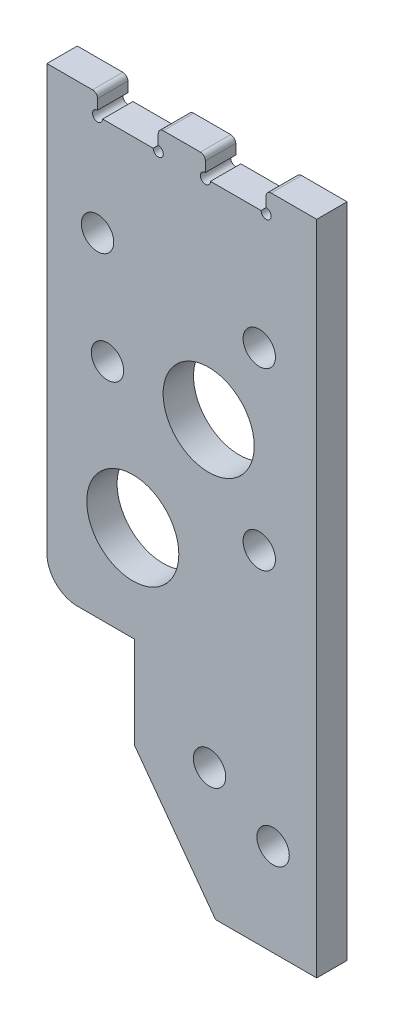
SolidWorks part; units mm, degrees
material "Thornel Mat VMA"
ref_plane "Front Plane" through (0, 0, 0) normal (0, 0, 1) x (1, 0, 0)
ref_plane "Top Plane" through (0, 0, 0) normal (0, 1, 0) x (1, 0, 0)
ref_plane "Right Plane" through (0, 0, 0) normal (1, 0, 0) x (0, 0, -1)
other "Configuration Table"
sketch "Sketch1" plane through (0, 0, 0) normal (0, 0, 1) x (1, 0, 0)
  line B0 (3.6623, 13.095) -> (3.6623, 3.9964)
  line B1 (3.6623, 3.9964) -> (11.6623, -6.905)
  line B2 (11.6623, -6.905) -> (21.6623, -6.905)
  line B3 (21.6623, -6.905) -> (21.6623, 13.095)
  line B4 (21.6623, 13.095) -> (3.6623, 13.095)
  line B5 (3.6623, 13.095) -> (0, 13.095)
  line B6 (-5, 6.5475) -> (-5, -6.905)
  line B7 (-5, -6.905) -> (11.6623, -6.905)
  line B8 (11.6623, -6.905) -> (3.6623, 3.9964)
  line B9 (3.6623, 3.9964) -> (3.6623, 13.095)
  circle B10 centre (11.0719, 5.8086) radius 1.6
  circle B11 centre (17.3507, 2.2242) radius 1.6
  ellipse B12 centre (0, 6.5475) end of major axis (0, 13.095) minor radius 5 (0, 13.095) -> (-5, 6.5475) ccw
sketch_block_instance "Block2-1"
sketch_block "Block2"
extrude "Boss-Extrude1" add sketch "Sketch1" along normal blind 3 contours B3 B4 B0 B1 B2 B11 B10 region at (13.4989, 3.97, 0)
sketch "Sketch2" plane through (0, 0, 3) normal (0, 0, 1) x (1, 0, 0)
  line L0 (21.6623, 13.095) -> (21.6623, 55.095)
  line L1 (21.6623, 55.095) -> (-5, 55.095)
  line L2 (-5, 55.095) -> (-5, 13.095)
  line L3 (-5, 13.095) -> (21.6623, 13.095)
  line L4 (-5, 6.5475) -> (-5, -6.905) construction
  line L5 (11.6623, -6.905) -> (21.6623, -6.905) construction
  dimension "D1" = 62
extrude "Boss-Extrude2" add sketch "Sketch2" against normal blind 3
fillet "Fillet1" radius 3 1 edges at (-5, 13.095, 1.5)
sketch "Sketch3" plane through (0, 0, 3) normal (0, 0, 1) x (1, 0, 0)
  line L0 (21.6623, 55.095) -> (-5, 55.095) construction
  line L1 (-5, 55.095) -> (-5, 16.095) construction
  line B0 (-5, 16.095) -> (-5, 55.095)
  line B1 (-5, 55.095) -> (21.6623, 55.095)
  line B2 (21.6623, 55.095) -> (21.6623, -6.905)
  circle B3 centre (-15.0778, 1.78) radius 21.35
  circle B4 centre (3.4846, 22.5419) radius 6.5
  line B5 (-26.1038, 1.78) -> (-9.6483, 1.78) construction
sketch_block_instance "Block3-2"
sketch_block "Block3" parameters "D1"=13, "D2"=42.7, "D3"=16.4555
sketch "Sketch4" plane through (0, 0, 3) normal (0, 0, 1) x (1, 0, 0)
  circle A0 centre (3.4846, 22.5419) radius 4.55
  dimension "D1" = 9.1
extrude "Cut-Extrude1" cut sketch "Sketch4" against normal blind 10
sketch "Sketch5" plane through (0, 0, 3) normal (0, 0, 1) x (1, 0, 0)
  line L0 (21.6623, 55.095) -> (21.6623, -6.905) construction
  line L1 (-5, 55.095) -> (21.6623, 55.095)
  line L2 (-5, 55.095) -> (-5, 50.095)
  line L3 (-5, 50.095) -> (21.6623, 50.095)
  line L4 (21.6623, 55.095) -> (21.6623, 50.095)
  dimension "D1" = 5
extrude "Cut-Extrude2" cut sketch "Sketch5" against normal blind 26.41
sketch "Sketch6" plane through (0, 0, 3) normal (0, 0, 1) x (1, 0, 0)
  line L5 (-5, 36.5075) -> (5.1299, 50.095)
  line L6 (-5, 16.095) -> (-5, 55.095) construction
  line L7 (-5, 50.095) -> (21.6623, 50.095) construction
  line L8 (5.1299, 50.095) -> (-5, 50.095)
  line L9 (-5, 50.095) -> (-5, 36.5075)
sketch "Sketch7" plane through (0, 0, 3) normal (0, 0, 1) x (1, 0, 0)
  line L0 (3.4846, 22.5419) -> (10.9846, 35.5323) construction
  line L1 (3.4846, 22.5419) -> (7.1669, 22.5419) construction
  circle A0 centre (10.9846, 35.5323) radius 4.5
  dimension "D2" = 9
  dimension "D1" = 15
  dimension "D3" = 60
extrude "Cut-Extrude4" cut sketch "Sketch7" against normal blind 26.41
sketch "Sketch8" plane through (0, 0, 3) normal (0, 0, 1) x (1, 0, 0)
  line L0 (15.9846, 44.1926) -> (3.4846, 22.5419) construction
  circle B0 centre (15.9846, 26.8721) radius 1.6
  circle B1 centre (15.9846, 44.1926) radius 1.6
  circle B2 centre (0.9846, 35.5323) radius 1.6
  arc B3 (13.4055, 25.3397) -> (18.6013, 28.3395) centre (15.9846, 26.8721) ccw
  arc B4 (17.4211, 34.6257) -> (18.6013, 28.3395) centre (27.3233, 33.2308) ccw
  arc B5 (17.4211, 34.6257) -> (17.4211, 36.439) centre (10.9846, 35.5323) ccw
  arc B6 (18.6013, 42.7252) -> (17.4211, 36.439) centre (27.3233, 37.8338) ccw
  arc B7 (18.6013, 42.7252) -> (13.4055, 45.7249) centre (15.9846, 44.1926) ccw
  arc B8 (8.5516, 41.5598) -> (13.4055, 45.7249) centre (4.8084, 50.8328) ccw
  arc B9 (8.5516, 41.5598) -> (6.9812, 40.6531) centre (10.9846, 35.5323) ccw
  arc B10 (0.9471, 38.5321) -> (6.9812, 40.6531) centre (0.8221, 48.5313) ccw
  arc B11 (0.9471, 38.5321) -> (0.9471, 32.5326) centre (0.9846, 35.5323) ccw
  arc B12 (6.9812, 30.4115) -> (0.9471, 32.5326) centre (0.8221, 22.5333) ccw
  arc B13 (6.9812, 30.4115) -> (8.5516, 29.5049) centre (10.9846, 35.5323) ccw
  arc B14 (13.4055, 25.3397) -> (8.5516, 29.5049) centre (4.8084, 20.2319) ccw
sketch_block_instance "Block1-1"
sketch_block "Block1"
extrude "Cut-Extrude5" cut sketch "Sketch8" against normal blind 10 contours B2 | B1 | B0 region at (15.9846, 26.8721, 3) region at (15.9846, 44.1926, 3) region at (0.9846, 35.5323, 3)
sketch "Sketch10" plane through (0, 0, 3) normal (0, 0, 1) x (1, 0, 0)
  line L0 (21.6623, -6.905) -> (21.6623, 50.095) construction
  line L1 (-5, 50.095) -> (21.6623, 50.095)
  line L2 (-5, 50.095) -> (-5, 58.036)
  line L3 (-5, 58.036) -> (21.6623, 58.036)
  line L4 (21.6623, 50.095) -> (21.6623, 58.036)
  line L5 (-5, 50.095) -> (-5, 16.095) construction
  line B0 (-5, 41.036) -> (-5, 56.036)
  line B1 (-5, 56.036) -> (5, 56.036)
  line B2 (5, 56.036) -> (5, 41.036)
  line B3 (5, 41.036) -> (-5, 41.036)
  circle B4 centre (0, 46.036) radius 1.6
  line M15 (21.6623, 50.095) -> (-5, 50.095)
  dimension "D1" = 2
sketch_block_instance "Block4-2"
sketch_block "Block4"
extrude "Cut-Extrude6" cut sketch "Sketch10" against normal blind 10 contours B4 region at (0, 46.036, 3)
extrude "Boss-Extrude3" add sketch "Sketch10<3>" against normal blind 3 contours B2 B1 L2 L1 | B1 B2 L4 L3 L2 M15 region at (0, 53.0655, 3) region at (11.5807, 54.4556, 3)
sketch "Sketch10<3>" plane through (0, 0, 3) normal (0, 0, 1) x (1, 0, 0) same geometry as "Sketch10"
sketch "Sketch12" plane through (0, 0, 3) normal (0, 0, 1) x (1, 0, 0)
  line L0 (-5, 58.036) -> (21.6623, 58.036) construction
  line L1 (0, 58.036) -> (6, 58.036)
  line L2 (0, 58.036) -> (0, 56.036)
  line L3 (0, 56.036) -> (6, 56.036)
  line L4 (6, 58.036) -> (6, 56.036)
  line L6 (-5, 58.036) -> (-5, 16.095) construction
  line L7 (10.6623, 58.036) -> (16.6623, 58.036)
  line L8 (10.6623, 58.036) -> (10.6623, 56.036)
  line L9 (10.6623, 56.036) -> (16.6623, 56.036)
  line L10 (16.6623, 58.036) -> (16.6623, 56.036)
  line L11 (21.6623, -6.905) -> (21.6623, 58.036) construction
  line L12 (-5, 56.036) -> (5, 56.036) construction
  dimension "D1" = 6
  dimension "D2" = 6
  dimension "D3" = 5
  dimension "D4" = 5
extrude "Cut-Extrude7" cut sketch "Sketch12" against normal blind 3
sketch "Sketch13" plane through (0, 0, 3) normal (0, 0, 1) x (1, 0, 0)
  circle A0 centre (0, 56.036) radius 0.5
  circle A1 centre (6, 56.036) radius 0.5
  circle A2 centre (10.6623, 56.036) radius 0.5
  circle A3 centre (16.6623, 56.036) radius 0.5
  dimension "D1" = 1
extrude "Cut-Extrude8" cut sketch "Sketch13" against normal blind 10
fillet "Fillet3" radius 0.5 4 edges at (16.6623, 58.036, 1.5) (10.6623, 58.036, 1.5) (6, 58.036, 1.5) (0, 58.036, 1.5)
